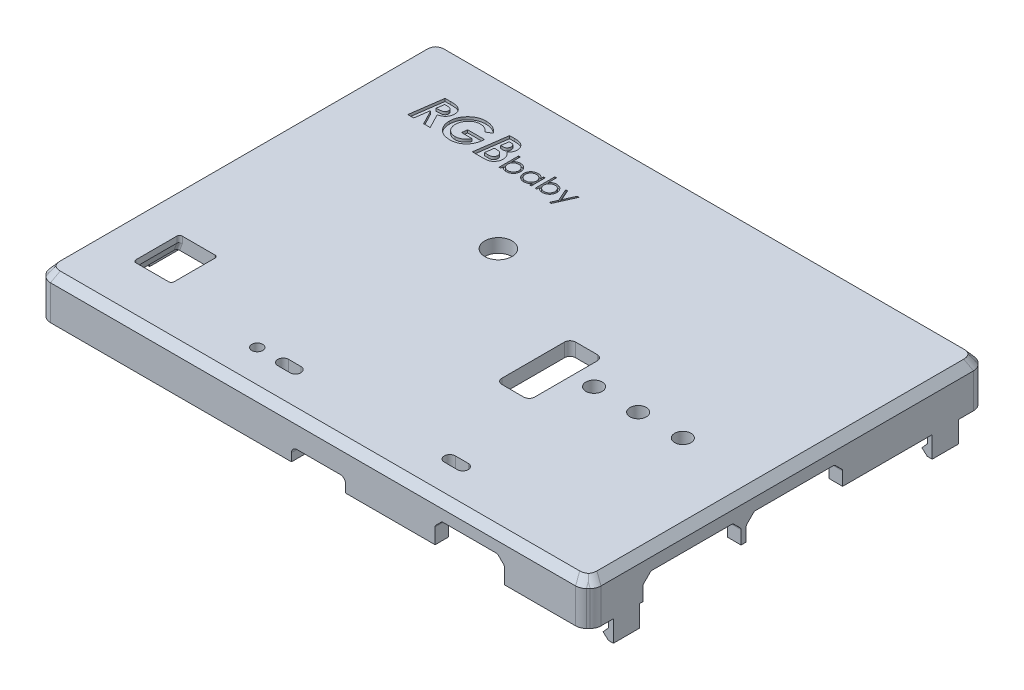
SolidWorks part; units mm, degrees
ref_plane "Front Plane" through (0, 0, 0) normal (0, 0, 1) x (1, 0, 0)
ref_plane "Top Plane" through (0, 0, 0) normal (0, 1, 0) x (1, 0, 0)
ref_plane "Right Plane" through (0, 0, 0) normal (1, 0, 0) x (0, 0, -1)
sketch "Sketch1" plane through (0, 0, 0) normal (0, 1, 0) x (1, 0, 0)
  line L1 (-50.5, -36.5) -> (50.5, -36.5)
  line L2 (-50.5, -36.5) -> (-50.5, 36.5)
  line L3 (-50.5, 36.5) -> (50.5, 36.5)
  line L4 (50.5, -36.5) -> (50.5, 36.5)
  line L5 (-50.5, -36.5) -> (50.5, 36.5) construction
  line L6 (-50.5, 36.5) -> (50.5, -36.5) construction
  point P0 (0, 0)
  dimension "D1" = 101
  dimension "D2" = 73
extrude "Boss-Extrude1" add sketch "Sketch1" along normal blind 7.85
shell "Shell3" thickness 2.5 removed face at (0, 0, 0)
sketch "Sketch2" plane through (0, 0, 36.5) normal (0, 0, 1) x (1, 0, 0)
  line L0 (-50.5, 0) -> (50.5, 0) construction
  line L1 (-3.96, 0) -> (5.98, 0)
  line L2 (-3.96, 0) -> (-3.96, 2.46)
  line L3 (-3.96, 2.46) -> (5.98, 2.46)
  line L4 (5.98, 0) -> (5.98, 2.46)
  line L5 (-3.96, 0) -> (5.98, 2.46) construction
  line L6 (-3.96, 2.46) -> (5.98, 0) construction
  line L8 (-3.96, 0) -> (-3.96, -0.7) construction
  line L9 (5.98, -0.7) -> (5.98, 0) construction
  point P4 (1.01, 1.23)
  dimension "D1" = 2.46
extrude "Cut-Extrude1" cut sketch "Sketch2" against normal blind 10
sketch "Sketch3" plane through (0, 0, 36.5) normal (0, 0, 1) x (1, 0, 0)
  line L0 (5.98, 0) -> (50.5, 0) construction
  line L1 (22.394, 0) -> (35.094, 0)
  line L2 (22.394, 0) -> (22.394, 4.29)
  line L3 (22.394, 4.29) -> (35.094, 4.29)
  line L4 (35.094, 0) -> (35.094, 4.29)
  line L5 (22.394, 0) -> (35.094, 4.29) construction
  line L6 (22.394, 4.29) -> (35.094, 0) construction
  line L7 (22.394, 0) -> (22.394, -1.21) construction
  line L8 (35.094, -1.21) -> (35.094, 0) construction
  point P4 (28.744, 2.145)
  dimension "D1" = 4.29
extrude "Cut-Extrude2" cut sketch "Sketch3" against normal blind 10
sketch "Sketch4" plane through (50.5, 0, 0) normal (1, 0, 0) x (0, 0, -1)
  line L0 (-36.5, 0) -> (36.5, 0) construction
  line L1 (-26.5, 0) -> (-8.4735, 0)
  line L2 (-26.5, 0) -> (-26.5, 4.15)
  line L3 (-26.5, 4.15) -> (-8.4735, 4.15)
  line L4 (-8.4735, 0) -> (-8.4735, 4.15)
  line L5 (-26.5, 0) -> (-8.4735, 4.15) construction
  line L6 (-26.5, 4.15) -> (-8.4735, 0) construction
  line L7 (-26.5, 0) -> (-26.5, -1.35) construction
  line L8 (-7.536, 0) -> (10.164, 0)
  line L9 (-7.536, 0) -> (-7.536, 4.15)
  line L10 (-7.536, 4.15) -> (10.164, 4.15)
  line L11 (10.164, 0) -> (10.164, 4.15)
  line L12 (-7.536, 0) -> (10.164, 4.15) construction
  line L13 (-7.536, 4.15) -> (10.164, 0) construction
  line L14 (-8.4735, -1.35) -> (-8.4735, 0) construction
  line L15 (-7.536, 0) -> (-7.536, -1.35) construction
  line L16 (10.164, -1.35) -> (10.164, 0) construction
  point P4 (-17.4867, 2.075)
  point P11 (1.314, 2.075)
  dimension "D1" = 4.15
extrude "Cut-Extrude3" cut sketch "Sketch4" against normal blind 10
sketch "Sketch5" plane through (0, 0, -36.5) normal (0, 0, -1) x (-1, 0, 0)
  line L0 (-50.5, 0) -> (50.5, 0) construction
  line L1 (-42.84, 0) -> (-20.66, 0)
  line L2 (-42.84, 0) -> (-42.84, 1.5)
  line L3 (-42.84, 1.5) -> (-20.66, 1.5)
  line L4 (-20.66, 0) -> (-20.66, 1.5)
  line L5 (-42.84, 0) -> (-20.66, 1.5) construction
  line L6 (-42.84, 1.5) -> (-20.66, 0) construction
  line L7 (-42.84, 0) -> (-42.84, -0.9) construction
  line L8 (-10.84, 0) -> (11.34, 0)
  line L9 (-10.84, 0) -> (-10.84, 1.5)
  line L10 (-10.84, 1.5) -> (11.34, 1.5)
  line L11 (11.34, 0) -> (11.34, 1.5)
  line L12 (-10.84, 0) -> (11.34, 1.5) construction
  line L13 (-10.84, 1.5) -> (11.34, 0) construction
  line L14 (21.16, 0) -> (43.34, 0)
  line L15 (21.16, 0) -> (21.16, 1.5)
  line L16 (21.16, 1.5) -> (43.34, 1.5)
  line L17 (43.34, 0) -> (43.34, 1.5)
  line L18 (21.16, 0) -> (43.34, 1.5) construction
  line L19 (21.16, 1.5) -> (43.34, 0) construction
  line L20 (-20.66, -0.9) -> (-20.66, 0) construction
  line L21 (-10.84, 0) -> (-10.84, -0.9) construction
  line L22 (11.34, -0.9) -> (11.34, 0) construction
  line L23 (21.16, 0) -> (21.16, -0.9) construction
  line L24 (43.34, -0.9) -> (43.34, 0) construction
  point P4 (-31.75, 0.75)
  point P11 (0.25, 0.75)
  point P16 (32.25, 0.75)
  dimension "D1" = 1.5
extrude "Cut-Extrude4" cut sketch "Sketch5" against normal blind 10
sketch "Sketch6" plane through (-50.5, 0, 0) normal (-1, 0, 0) x (0, 0, 1)
  line L0 (-36.5, 0) -> (36.5, 0) construction
  line L1 (-5.64, 0) -> (12.54, 0)
  line L2 (-5.64, 0) -> (-5.64, 1.5)
  line L3 (-5.64, 1.5) -> (12.54, 1.5)
  line L4 (12.54, 0) -> (12.54, 1.5)
  line L5 (-5.64, 0) -> (12.54, 1.5) construction
  line L6 (-5.64, 1.5) -> (12.54, 0) construction
  line L7 (-5.64, 0) -> (-5.64, -0.9) construction
  line L8 (12.54, -0.9) -> (12.54, 0) construction
  point P4 (3.45, 0.75)
  dimension "D1" = 1.5
extrude "Cut-Extrude5" cut sketch "Sketch6" against normal blind 10
sketch "Sketch7" plane through (-50.5, 0, 0) normal (-1, 0, 0) x (0, 0, 1)
  line L0 (12.54, 0) -> (36.5, 0) construction
  line L1 (18.5, 0) -> (26.5, 0)
  line L2 (18.5, 0) -> (18.5, 5)
  line L3 (18.5, 5) -> (26.5, 5)
  line L4 (26.5, 0) -> (26.5, 5)
  line L5 (18.5, 0) -> (26.5, 5) construction
  line L6 (18.5, 5) -> (26.5, 0) construction
  line L7 (18.5, 0) -> (18.5, -1.4) construction
  line L8 (26.5, -1.4) -> (26.5, 0) construction
  point P4 (22.5, 2.5)
  dimension "D1" = 5
extrude "Cut-Extrude6" cut sketch "Sketch7" against normal blind 10
fillet "Fillet1" radius 0.5 8 edges at (-49.25, 1.5, 12.54) (-49.25, 1.5, -5.64) (-43.34, 1.5, -35.25) (-21.16, 1.5, -35.25) (-11.34, 1.5, -35.25) (10.84, 1.5, -35.25) (20.66, 1.5, -35.25) (42.84, 1.5, -35.25)
fillet "Fillet2" radius 1 2 edges at (5.98, 2.46, 35.25) (-3.96, 2.46, 35.25)
chamfer "Chamfer1" distance 1.25 angle 45 2 edges at (35.094, 4.29, 35.25) (22.394, 4.29, 35.25)
chamfer "Chamfer2" distance 1.5 angle 45 4 edges at (49.25, 4.15, -10.164) (49.25, 4.15, 7.536) (49.25, 4.15, 8.4735) (49.25, 4.15, 26.5)
fillet "Fillet3" radius 0.5 12 edges at (23.644, 4.29, 35.25) (22.394, 3.04, 35.25) (33.844, 4.29, 35.25) (35.094, 3.04, 35.25) (49.25, 4.15, 25) (49.25, 2.65, 26.5) (49.25, 4.15, 9.9735) (49.25, 2.65, 8.4735) (49.25, 2.65, 7.536) (49.25, 4.15, 6.036) (49.25, 2.65, -10.164) (49.25, 4.15, -8.664)
chamfer "Chamfer3" distance 1.5 angle 45 4 edges at (-50.5, 3.925, -36.5) (50.5, 3.925, -36.5) (50.5, 3.925, 36.5) (-50.5, 3.925, 36.5)
chamfer "Chamfer4" distance 1.5 angle 40 8 edges at (49.75, 7.85, -35.75) (50.5, 7.85, 0) (49.75, 7.85, 35.75) (0, 7.85, 36.5) (-49.75, 7.85, 35.75) (-50.5, 7.85, 0) (-49.75, 7.85, -35.75) (0, 7.85, -36.5) first distance on face at (49.75, 3.925, -35.75) first distance on face at (50.5, 2.8946, 6.7386) first distance on face at (49.75, 3.925, 35.75) first distance on face at (14.675, 2.648, 36.5) first distance on face at (-49.75, 3.925, 35.75) first distance on face at (-50.5, 2.2077, 7.9071) first distance on face at (-49.75, 3.925, -35.75) first distance on face at (-0.2045, 1.4237, -36.5)
fillet "Fillet4" radius 2 8 edges at (50.5, 3.175, 35) (49, 3.175, 36.5) (-49, 3.175, 36.5) (-50.5, 3.175, 35) (-50.5, 3.175, -35) (-49, 3.175, -36.5) (49, 3.175, -36.5) (50.5, 3.175, -35)
fillet "Fillet5" radius 2.6 8 edges at (-48.7078, 7.1907, -35.7946) (-49.7946, 7.1907, -34.7078) (48.7078, 7.1907, -35.7946) (49.7946, 7.1907, -34.7078) (49.7946, 7.1907, 34.7078) (48.7078, 7.1907, 35.7946) (-48.7078, 7.1907, 35.7946) (-49.7946, 7.1907, 34.7078)
sketch "Sketch8" plane through (0, 7.85, 0) normal (0, 1, 0) x (1, 0, 0)
  line L0 (-43, -24.8) -> (-43, -26) construction
  line L1 (-42.5, -18.5) -> (-35.5, -18.5)
  line L2 (-42.5, -18.5) -> (-42.5, -27)
  line L3 (-42.5, -27) -> (-35.5, -27)
  line L4 (-35.5, -18.5) -> (-35.5, -27)
  line L5 (-42.5, -18.5) -> (-35.5, -27) construction
  line L6 (-42.5, -27) -> (-35.5, -18.5) construction
  line L7 (-43, -26) -> (-36, -26) construction
  line L8 (-36, -19) -> (-36, -26) construction
  line L9 (-43, -19) -> (-36, -19) construction
  point P4 (-39, -22.75)
  dimension "D1" = 0.5
  dimension "D2" = 1
  dimension "D3" = 0.5
  dimension "D4" = 0.5
extrude "Cut-Extrude7" cut sketch "Sketch8" against normal blind 5
chamfer "Chamfer5" distance 0.5 angle 70 1 edges at (-42.5, 5.35, 22.75) first distance on face at (-39, 5.35, 22.75)
sketch "Sketch9" plane through (0, 5.35, 0) normal (0, -1, 0) x (1, 0, 0)
  line L0 (0, 0) -> (0, -0.75) construction
  line L1 (15.9, -0.75) -> (9.9, -0.75)
  line L2 (15.9, -0.75) -> (15.9, 12.75)
  line L3 (15.9, 12.75) -> (9.9, 12.75)
  line L4 (9.9, -0.75) -> (9.9, 12.75)
  line L5 (15.9, -0.75) -> (9.9, 12.75) construction
  line L6 (15.9, 12.75) -> (9.9, -0.75) construction
  line L7 (20.35, 30.37) -> (17.9613, 30.37)
  line L8 (20.35, 28.37) -> (17.9613, 28.37)
  line L9 (-10.4, 28.3262) -> (-12.65, 28.3262)
  line L10 (-10.4, 30.3262) -> (-12.65, 30.3262)
  line L11 (0, -0.75) -> (9.9, -0.75) construction
  circle A0 centre (20.35, 29.37) radius 1
  circle A1 centre (17.9613, 29.37) radius 1
  circle A2 centre (-10.4, 29.3262) radius 1
  circle A3 centre (-12.65, 29.3262) radius 1
  circle A4 centre (-17.4387, 29.3012) radius 1
  circle A6 centre (19.7, 4.65) radius 1.5
  circle A7 centre (27.8, 4.65) radius 1.5
  circle A8 centre (36, 4.65) radius 1.5
  circle A9 centre (-11, -8.5) radius 2.5
  point P32 (12.9, 6)
  dimension "D1" = 3
  dimension "D2" = 2
  dimension "D3" = 5
  dimension "D4" = 6
  dimension "D5" = 13.5
  dimension "D6" = 0.75
  dimension "D7" = 9.9
extrude "Cut-Extrude8" cut sketch "Sketch9" against normal through all contours A0 | A1 L8 A0 L7 | A1 | A2 | A3 L9 A2 L10 | A3 | L4 L1 L2 L3 | A8 | A7 | A6 | A9 | A4 region at (12.9, 5.35, 6) region at (19.1556, 5.35, 29.37) region at (20.35, 5.35, 29.37) region at (17.9613, 5.35, 29.37) region at (-11.525, 5.35, 29.3263) region at (-10.4, 5.35, 29.3262) region at (-12.65, 5.35, 29.3262) region at (19.7, 5.35, 4.65) region at (27.8, 5.35, 4.65) region at (36, 5.35, 4.65) region at (-11, 5.35, -8.5)
fillet "Fillet6" radius 1 4 edges at (9.9, 6.6, 12.75) (15.9, 6.6, 12.75) (15.9, 6.6, -0.75) (9.9, 6.6, -0.75)
sketch "Sketch10" plane through (0, 7.85, 0) normal (0, 1, 0) x (1, 0, 0)
  line L0 (-49.2414, 21.5) -> (-24.2414, 21.5) construction
  line L1 (-49.2414, 33.6537) -> (-49.2414, -33.6537) construction
  line L2 (-48.1716, 36.5) -> (48.1716, 36.5) construction
  line L3 (-24.2414, 21.5) -> (-14.2414, 21.5) construction
  text T0 "<b><i>RGB</i></b>" font "Century Gothic" height 6
  text T1 "baby"
  dimension "D1" = 15
  dimension "D2" = 10
  dimension "D3" = 25
extrude "Cut-Extrude9" cut sketch "Sketch10" against normal blind 0.5
fillet "Fillet7" radius 0.5 6 edges at (-35.5, 6.6, 18.5) (-42.5, 7.2869, 18.5) (-42.75, 6.0369, 18.5) (-42.5, 7.2869, 27) (-42.75, 6.0369, 27) (-35.5, 6.6, 27)
sketch "Sketch11" plane through (0, 0, 0) normal (0, -1, 0) x (1, 0, 0)
  line L0 (50.5, 34.1716) -> (50.5, 26.5) construction
  line L1 (50.5, 31.9) -> (49.6, 31.9)
  line L2 (50.5, 31.9) -> (50.5, 27.1)
  line L3 (50.5, 27.1) -> (49.6, 27.1)
  line L4 (49.6, 31.9) -> (49.6, 27.1)
  line L5 (50.5, 31.9) -> (49.6, 27.1) construction
  line L6 (50.5, 27.1) -> (49.6, 31.9) construction
  line L7 (50.5, 32) -> (49.5, 32) construction
  line L8 (49.5, 27) -> (49.5, 32) construction
  line L9 (50.5, 27) -> (49.5, 27) construction
  point P4 (50.05, 29.5)
  dimension "D1" = 0.1
  dimension "D2" = 0.1
  dimension "D3" = 0.1
extrude "Boss-Extrude2" add sketch "Sketch11" along normal offset from surface (3.9 mm away) 0.1
sketch "Sketch12" plane through (0, 0, 0) normal (0, -1, 0) x (1, 0, 0)
  line L0 (50.5, -10.164) -> (50.5, -34.1716) construction
  line L1 (50.5, -26.6) -> (49.6, -26.6)
  line L2 (50.5, -26.6) -> (50.5, -31.4)
  line L3 (50.5, -31.4) -> (49.6, -31.4)
  line L4 (49.6, -26.6) -> (49.6, -31.4)
  line L5 (50.5, -26.6) -> (49.6, -31.4) construction
  line L6 (50.5, -31.4) -> (49.6, -26.6) construction
  line L7 (50.5, -26.5) -> (49.5, -26.5) construction
  line L8 (49.5, -26.5) -> (49.5, -31.5) construction
  line L9 (50.5, -31.5) -> (49.5, -31.5) construction
  point P4 (50.05, -29)
  dimension "D1" = 0.1
  dimension "D2" = 0.1
  dimension "D3" = 0.1
extrude "Boss-Extrude3" add sketch "Sketch12" along normal offset from surface (3.9 mm away) 0.1
sketch "Sketch13" plane through (0, 0, 0) normal (0, -1, 0) x (1, 0, 0)
  line L0 (-50.5, -34.1716) -> (-50.5, -5.64) construction
  line L1 (-50.5, -31.4) -> (-49.6, -31.4)
  line L2 (-50.5, -31.4) -> (-50.5, -26.6)
  line L3 (-50.5, -26.6) -> (-49.6, -26.6)
  line L4 (-49.6, -31.4) -> (-49.6, -26.6)
  line L5 (-50.5, -31.4) -> (-49.6, -26.6) construction
  line L6 (-50.5, -26.6) -> (-49.6, -31.4) construction
  line L7 (-50.5, -31.5) -> (-49.5, -31.5) construction
  line L8 (-49.5, -26.5) -> (-49.5, -31.5) construction
  line L9 (-50.5, -26.5) -> (-49.5, -26.5) construction
  point P4 (-50.05, -29)
  dimension "D1" = 0.1
  dimension "D2" = 0.1
  dimension "D3" = 0.1
extrude "Boss-Extrude4" add sketch "Sketch13" along normal offset from surface (3.9 mm away) 0.1
sketch "Sketch15" plane through (0, 0, 0) normal (0, -1, 0) x (1, 0, 0)
  line L0 (-50.5, 26.5) -> (-50.5, 34.1716) construction
  line L1 (-50.5, 27.1) -> (-49.6, 27.1)
  line L2 (-50.5, 27.1) -> (-50.5, 31.9)
  line L3 (-50.5, 31.9) -> (-49.6, 31.9)
  line L4 (-49.6, 27.1) -> (-49.6, 31.9)
  line L5 (-50.5, 27.1) -> (-49.6, 31.9) construction
  line L6 (-50.5, 31.9) -> (-49.6, 27.1) construction
  line L7 (-50.5, 27) -> (-49.5, 27) construction
  line L9 (-50.5, 32) -> (-49.5, 32) construction
  line L10 (-49.5, 27) -> (-49.5, 32) construction
  point P4 (-50.05, 29.5)
  dimension "D1" = 0.1
  dimension "D2" = 0.1
  dimension "D3" = 0.1
extrude "Boss-Extrude6" add sketch "Sketch15" along normal offset from surface (3.9 mm away) 0.1
sketch "Sketch16" plane through (0, 0, -31.4) normal (0, 0, -1) x (-1, 0, 0)
  line L0 (-49.6, -1.9) -> (-48.6078, -3.025)
  line L1 (-49.6, -3.9) -> (-49.6, 0) construction
  line L2 (-48.6078, -3.025) -> (-49.6, -3.9)
  line L3 (49.6, -3.9) -> (48.6078, -3.025)
  line L4 (48.6078, -3.025) -> (49.6, -1.9)
  line L5 (49.6, -3.9) -> (49.6, 0) construction
  line L6 (49.6, -3.9) -> (49.6, -1.9)
  line L7 (-49.6, -1.9) -> (-49.6, -3.9)
  dimension "D1" = 2
  dimension "D2" = 41.41
  dimension "D3" = 1.5
  dimension "D4" = 2
  dimension "D5" = 1.5
  dimension "D6" = 41.41
extrude "Boss-Extrude7" add sketch "Sketch16" against normal up to surface (4.8 mm away) up to face at (50.05, -1.95, -26.6)
sketch "Sketch17" plane through (0, 0, 31.9) normal (0, 0, 1) x (1, 0, 0)
  line L0 (49.6, -3.9) -> (48.6078, -3.025)
  line L1 (48.6078, -3.025) -> (49.6, -1.9)
  line L2 (49.6, -3.9) -> (49.6, 0) construction
  line L3 (49.6, -1.9) -> (49.6, -3.9)
  line L4 (-49.6, -3.9) -> (-48.6078, -3.025)
  line L5 (-48.6078, -3.025) -> (-49.6, -1.9)
  line L6 (-49.6, -3.9) -> (-49.6, 0) construction
  line L7 (-49.6, -1.9) -> (-49.6, -3.9)
  dimension "D1" = 2
  dimension "D2" = 41.41
  dimension "D3" = 1.5
  dimension "D4" = 2
  dimension "D5" = 41.41
  dimension "D6" = 1.5
extrude "Boss-Extrude8" add sketch "Sketch17" against normal up to surface (4.8 mm away) up to face at (-50.05, -1.95, 27.1)
